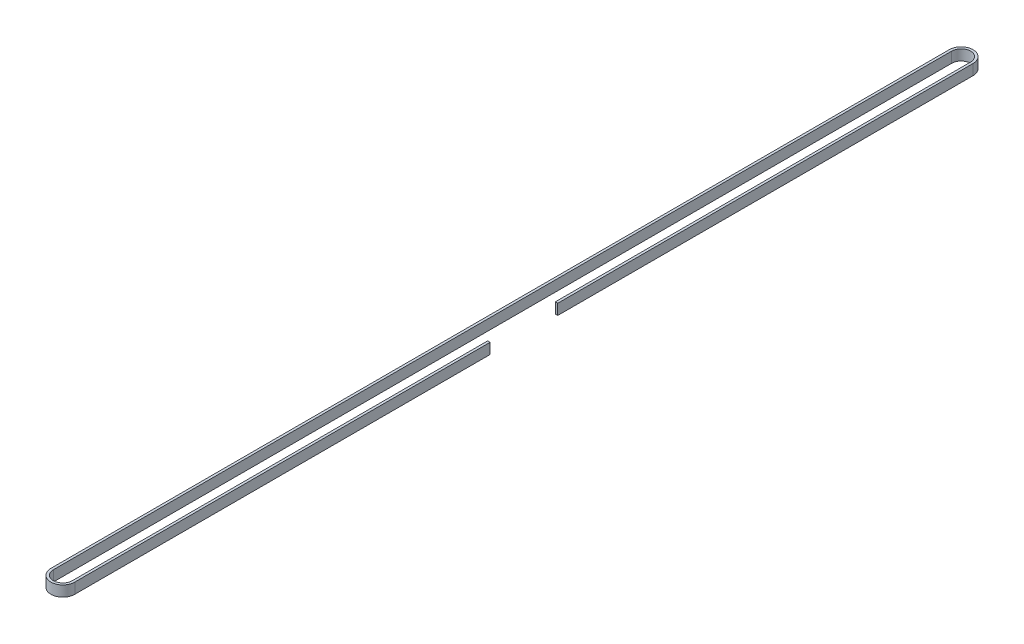
SolidWorks part; units mm, degrees
ref_plane "Front Plane" through (0, 0, 0) normal (0, 0, 1) x (1, 0, 0)
ref_plane "Top Plane" through (0, 0, 0) normal (0, 1, 0) x (1, 0, 0)
ref_plane "Right Plane" through (0, 0, 0) normal (1, 0, 0) x (0, 0, -1)
sketch "Sketch1" plane through (0, 0, 0) normal (0, 1, 0) x (1, 0, 0)
  line L0 (344.01, -294.7675) -> (344.01, 213.4825)
  line L1 (356.75, 213.4825) -> (356.75, -21.5175)
  line L2 (356.75, -294.7675) -> (356.75, -59.7675)
  arc A0 (356.75, -294.7675) -> (344.01, -294.7675) centre (350.38, -294.7675) cw
  arc A1 (356.75, 213.4825) -> (344.01, 213.4825) centre (350.38, 213.4825) ccw
  dimension "D1" = 6.37
  dimension "D2" = 508.25
  dimension "D3" = 235
extrude "Extrude-Thin1" add sketch "Sketch1" along normal blind 6 thin thin type two direction wall 0.376 second wall 1.004
